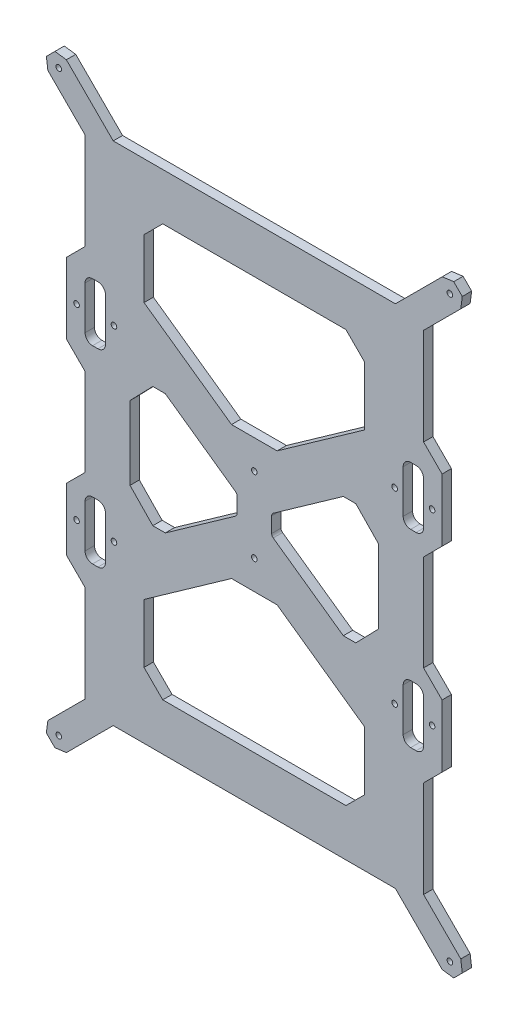
SolidWorks part; units mm, degrees
ref_plane "Piano frontale" through (0, 0, 0) normal (0, 0, 1) x (1, 0, 0)
ref_plane "Piano superiore" through (0, 0, 0) normal (0, 1, 0) x (1, 0, 0)
ref_plane "Piano destro" through (0, 0, 0) normal (1, 0, 0) x (0, 0, -1)
sketch "Schizzo1" plane through (0, 0, 0) normal (0, 0, 1) x (1, 0, 0)
  line L0 (-66.4357, 19.6293) -> (-66.4357, -19.6293)
  line L1 (-86.4486, 39.007) -> (-83.5514, 39.007) construction
  line L2 (-111.1309, 156.5575) -> (-106.5575, 161.1309)
  line L3 (-85, 39.007) -> (-85, 72.1548) construction
  line L4 (-111.1309, 156.5575) -> (-110.3308, 150.4313)
  line L5 (-110.3308, 150.4313) -> (-90.4486, 130.5491)
  line L6 (-90.4486, 130.5491) -> (-90.4486, 78.8741)
  line L7 (-90.4486, 78.8741) -> (-100.3308, 68.992)
  line L8 (-90.4486, 21.1259) -> (-90.4486, -25.6817)
  line L9 (-9.2567, 4.0961) -> (-9.2567, -4.0961)
  line L10 (0, 0) -> (-165.9293, 0) construction
  line L11 (-58.9422, 100.14) -> (-58.9422, 68.7002)
  line L12 (-58.9422, 100.14) -> (-48.9422, 110.14)
  line L13 (-86.4486, 35.007) -> (-83.5514, 35.007)
  line L14 (-75, 50) -> (-107.9533, 50) construction
  line L15 (-79.5514, 39.007) -> (-79.5514, 62.007)
  line L16 (-104.5, 154.5) -> (0, 50) construction
  line L17 (-106.5575, 161.1309) -> (-100.4313, 160.3308)
  line L18 (75, 50) -> (107.9533, 50) construction
  line L19 (85, 39.007) -> (85, 72.1548) construction
  line L20 (86.4486, 39.007) -> (83.5514, 39.007) construction
  line L21 (86.4486, 66.007) -> (83.5514, 66.007)
  line L22 (0, 0) -> (0, 265.525) construction
  line L23 (90.4486, 39.007) -> (90.4486, 62.007)
  line L24 (-100.3308, 68.992) -> (-100.3308, 31.008)
  line L25 (-90.4486, 21.1259) -> (-100.3308, 31.008)
  line L26 (100.4313, 160.3308) -> (75.3933, 135.2928)
  line L27 (47.5638, 32.2218) -> (10.1019, 5.729)
  line L28 (54.2431, 32.2218) -> (47.5638, 32.2218)
  line L29 (-58.9422, 68.7002) -> (-12.1818, 35.6316)
  line L30 (-12.1818, 35.6316) -> (12.1818, 35.6316)
  line L31 (66.4357, 19.6293) -> (54.2431, 32.2218)
  line L32 (58.9422, 68.7002) -> (12.1818, 35.6316)
  line L33 (-75.3933, 135.2928) -> (75.3933, 135.2928)
  line L34 (90.4486, 25.6817) -> (100.3308, 35.5638)
  line L35 (100.3308, 68.992) -> (100.3308, 35.5638)
  line L36 (106.5575, 161.1309) -> (100.4313, 160.3308)
  line L37 (79.5514, 39.007) -> (79.5514, 62.007)
  line L38 (-66.4357, 19.6293) -> (-54.2431, 32.2218)
  line L39 (-54.2431, 32.2218) -> (-47.5638, 32.2218)
  line L40 (-47.5638, 32.2218) -> (-10.1019, 5.729)
  line L41 (86.4486, 35.007) -> (83.5514, 35.007)
  line L42 (58.9422, 100.14) -> (48.9422, 110.14)
  line L43 (58.9422, 100.14) -> (58.9422, 68.7002)
  line L44 (9.2567, 4.0961) -> (9.2567, -4.0961)
  line L45 (90.4486, 25.6817) -> (90.4486, -25.6817)
  line L46 (90.4486, 78.8741) -> (100.3308, 68.992)
  line L47 (90.4486, 130.5491) -> (90.4486, 78.8741)
  line L48 (110.3308, 150.4313) -> (90.4486, 130.5491)
  line L49 (111.1309, 156.5575) -> (110.3308, 150.4313)
  line L50 (111.1309, 156.5575) -> (106.5575, 161.1309)
  line L51 (66.4357, 19.6293) -> (66.4357, -19.6293)
  line L52 (-48.9422, 110.14) -> (48.9422, 110.14)
  line L53 (86.4486, -39.007) -> (83.5514, -39.007) construction
  line L54 (85, -39.007) -> (85, -72.1548) construction
  line L55 (75, -50) -> (107.9533, -50) construction
  line L56 (-75, -50) -> (-107.9533, -50) construction
  line L57 (-85, -39.007) -> (-85, -72.1548) construction
  line L58 (-86.4486, -39.007) -> (-83.5514, -39.007) construction
  line L59 (-86.4486, -66.007) -> (-83.5514, -66.007)
  line L60 (-90.4486, -39.007) -> (-90.4486, -62.007)
  line L61 (-100.4313, -160.3308) -> (-75.3933, -135.2928)
  line L62 (-48.9422, -110.14) -> (48.9422, -110.14)
  line L63 (-100.4313, 160.3308) -> (-75.3933, 135.2928)
  line L64 (111.1309, -156.5575) -> (106.5575, -161.1309)
  line L65 (111.1309, -156.5575) -> (110.3308, -150.4313)
  line L66 (110.3308, -150.4313) -> (90.4486, -130.5491)
  line L67 (90.4486, -130.5491) -> (90.4486, -78.8741)
  line L68 (90.4486, -78.8741) -> (100.3308, -68.992)
  line L69 (58.9422, -100.14) -> (58.9422, -68.7002)
  line L70 (58.9422, -100.14) -> (48.9422, -110.14)
  line L71 (86.4486, -35.007) -> (83.5514, -35.007)
  line L72 (-47.5638, -32.2218) -> (-10.1019, -5.729)
  line L73 (-54.2431, -32.2218) -> (-47.5638, -32.2218)
  line L74 (-90.4486, 39.007) -> (-90.4486, 62.007)
  line L75 (-86.4486, 66.007) -> (-83.5514, 66.007)
  line L76 (-66.4357, -19.6293) -> (-54.2431, -32.2218)
  line L77 (79.5514, -39.007) -> (79.5514, -62.007)
  line L78 (106.5575, -161.1309) -> (100.4313, -160.3308)
  line L79 (100.3308, -68.992) -> (100.3308, -35.5638)
  line L80 (90.4486, -25.6817) -> (100.3308, -35.5638)
  line L81 (-75.3933, -135.2928) -> (75.3933, -135.2928)
  line L82 (58.9422, -68.7002) -> (12.1818, -35.6316)
  line L83 (66.4357, -19.6293) -> (54.2431, -32.2218)
  line L84 (-12.1818, -35.6316) -> (12.1818, -35.6316)
  line L85 (-58.9422, -68.7002) -> (-12.1818, -35.6316)
  line L86 (54.2431, -32.2218) -> (47.5638, -32.2218)
  line L87 (47.5638, -32.2218) -> (10.1019, -5.729)
  line L88 (100.4313, -160.3308) -> (75.3933, -135.2928)
  line L89 (-90.4486, -25.6817) -> (-100.3308, -35.5638)
  line L90 (-100.3308, -68.992) -> (-100.3308, -35.5638)
  line L91 (90.4486, -39.007) -> (90.4486, -62.007)
  line L92 (86.4486, -66.007) -> (83.5514, -66.007)
  line L93 (-106.5575, -161.1309) -> (-100.4313, -160.3308)
  line L94 (-79.5514, -39.007) -> (-79.5514, -62.007)
  line L95 (-86.4486, -35.007) -> (-83.5514, -35.007)
  line L96 (-58.9422, -100.14) -> (-48.9422, -110.14)
  line L97 (-58.9422, -100.14) -> (-58.9422, -68.7002)
  line L98 (-90.4486, -78.8741) -> (-100.3308, -68.992)
  line L99 (-90.4486, -130.5491) -> (-90.4486, -78.8741)
  line L100 (-110.3308, -150.4313) -> (-90.4486, -130.5491)
  line L101 (-111.1309, -156.5575) -> (-110.3308, -150.4313)
  line L102 (-111.1309, -156.5575) -> (-106.5575, -161.1309)
  circle A0 centre (-95, 50) radius 1.5
  circle A1 centre (-75, 50) radius 1.5
  arc A2 (-79.5514, 39.007) -> (-83.5514, 35.007) centre (-83.5514, 39.007) cw
  arc A3 (-83.5514, 66.007) -> (-79.5514, 62.007) centre (-83.5514, 62.007) cw
  arc A4 (9.2567, 4.0961) -> (10.1019, 5.729) centre (11.2567, 4.0961) cw
  arc A5 (90.4486, 39.007) -> (86.4486, 35.007) centre (86.4486, 39.007) cw
  circle A6 centre (-104.5, 154.5) radius 1.5
  arc A7 (86.4486, 66.007) -> (90.4486, 62.007) centre (86.4486, 62.007) cw
  circle A8 centre (104.5, 154.5) radius 1.5
  arc A9 (83.5514, 66.007) -> (79.5514, 62.007) centre (83.5514, 62.007) ccw
  arc A10 (79.5514, 39.007) -> (83.5514, 35.007) centre (83.5514, 39.007) ccw
  circle A11 centre (75, 50) radius 1.5
  circle A12 centre (95, 50) radius 1.5
  arc A13 (-9.2567, -4.0961) -> (-10.1019, -5.729) centre (-11.2567, -4.0961) cw
  arc A14 (-90.4486, -39.007) -> (-86.4486, -35.007) centre (-86.4486, -39.007) cw
  circle A15 centre (0, 20.1313) radius 1.5
  arc A16 (-86.4486, -66.007) -> (-90.4486, -62.007) centre (-86.4486, -62.007) cw
  arc A17 (-86.4486, 66.007) -> (-90.4486, 62.007) centre (-86.4486, 62.007) ccw
  circle A18 centre (0, -20.1313) radius 1.5
  arc A19 (-90.4486, 39.007) -> (-86.4486, 35.007) centre (-86.4486, 39.007) ccw
  circle A20 centre (95, -50) radius 1.5
  circle A21 centre (75, -50) radius 1.5
  arc A22 (79.5514, -39.007) -> (83.5514, -35.007) centre (83.5514, -39.007) cw
  arc A23 (83.5514, -66.007) -> (79.5514, -62.007) centre (83.5514, -62.007) cw
  circle A24 centre (104.5, -154.5) radius 1.5
  arc A25 (86.4486, -66.007) -> (90.4486, -62.007) centre (86.4486, -62.007) ccw
  circle A26 centre (-104.5, -154.5) radius 1.5
  arc A27 (90.4486, -39.007) -> (86.4486, -35.007) centre (86.4486, -39.007) ccw
  arc A28 (9.2567, -4.0961) -> (10.1019, -5.729) centre (11.2567, -4.0961) ccw
  arc A29 (-83.5514, -66.007) -> (-79.5514, -62.007) centre (-83.5514, -62.007) ccw
  arc A30 (-9.2567, 4.0961) -> (-10.1019, 5.729) centre (-11.2567, 4.0961) ccw
  arc A31 (-79.5514, -39.007) -> (-83.5514, -35.007) centre (-83.5514, -39.007) ccw
  circle A32 centre (-75, -50) radius 1.5
  circle A33 centre (-95, -50) radius 1.5
  point P1 (-58.9422, -110.14)
  point P10 (-90.4486, 0)
  point P14 (-85, 35.007)
  point P22 (-85, 66.007)
  point P26 (-108.8442, 158.8442)
  point P66 (-66.4357, 0)
  point P69 (0, 110.14)
  point P72 (-100.3308, 50)
  point P77 (0, 135.2928)
  point P78 (0, 35.6316)
  point P88 (9.2567, 0)
  point P94 (58.9422, 110.14)
  point P96 (108.8442, 158.8442)
  point P97 (85, 66.007)
  point P98 (85, 35.007)
  point P133 (-58.9422, 110.14)
  point P167 (66.4357, 0)
  point P174 (90.4486, 0)
  point P194 (-9.2567, 0)
  point P198 (-66.4357, 0)
  point P199 (85, -35.007)
  point P200 (85, -66.007)
  point P201 (108.8442, -158.8442)
  point P203 (58.9422, -110.14)
  point P204 (0, -35.6316)
  point P205 (0, -135.2928)
  point P207 (0, -110.14)
  point P208 (-108.8442, -158.8442)
  point P209 (-85, -66.007)
  point P210 (-85, -35.007)
  dimension "D1" = 154.5
  dimension "D2" = 104.5
  dimension "D3" = 20
  dimension "D5" = 2
  dimension "D6" = 85
  dimension "D7" = 23
  dimension "D8" = 45
  dimension "D9" = 14
  dimension "D10" = 50
extrude "Estrusione-Estrusione1" add sketch "Schizzo1" against normal blind 5
sketch "Schizzo2" plane through (0, 0, 0) normal (0, 0, 1) x (1, 0, 0)
  line L0 (0, 0) -> (0, 148.2594) construction
  line L1 (58.9422, 84.4201) -> (-108.2298, 84.4201) construction
  line L2 (58.9422, 68.7002) -> (58.9422, 100.14) construction
  line L3 (0, 0) -> (-115.6703, 0) construction
  point P0 (29.4418, 84.4201)
  point P8 (-29.4418, 84.4201)
  point P10 (-55.8026, 0)
  point P12 (-29.4418, 0)
  point P13 (55.8026, 0)
  point P14 (29.4418, 0)
  point P15 (29.4418, -84.4201)
  point P16 (-29.4418, -84.4201)
